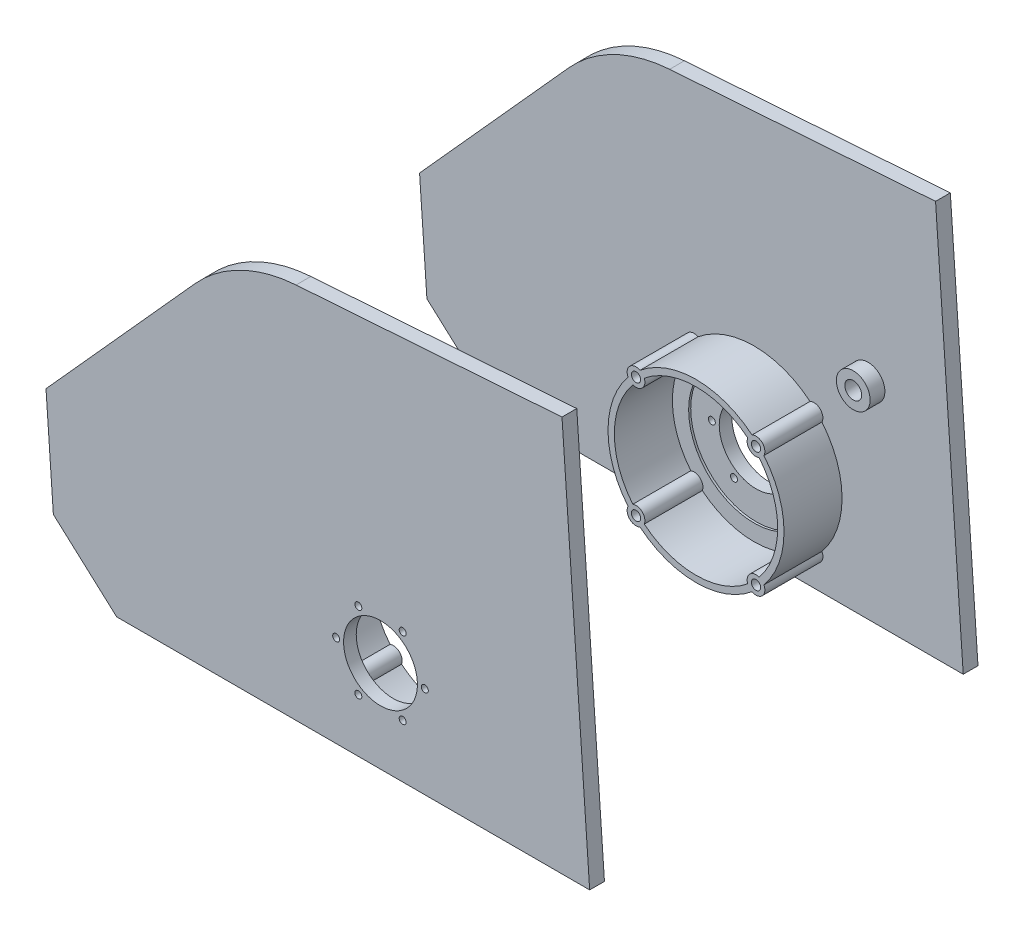
SolidWorks part; units mm, degrees
note: The reader was unsure of these and kept them because the rebuilt part matched: shared geometry of "Sketch4<9>", "Sketch4<11>", "Sketch4<12>", "Sketch2<13>", "Sketch2<14>".
material "ABS"
ref_plane "Front Plane" through (0, 0, 0) normal (0, 0, 1) x (1, 0, 0)
ref_plane "Top Plane" through (0, 0, 0) normal (0, 1, 0) x (1, 0, 0)
ref_plane "Right Plane" through (0, 0, 0) normal (1, 0, 0) x (0, 0, -1)
sketch "Sketch1" plane through (0, 0, 0) normal (0, 0, 1) x (1, 0, 0)
  line L0 (-158.4878, 33.3903) -> (-155, -16.4879)
  line L1 (-155, -16.4879) -> (-125, -43.5)
  line L2 (-125, -43.5) -> (99.1113, -43.5)
  line L3 (-40, 135.1892) -> (86, 144)
  line L5 (-158.4878, 33.3903) -> (-87.8345, 111.8588)
  line L7 (99.1113, -43.5) -> (86, 144)
  line L8 (0, 0) -> (54, 54) construction
  line L11 (-47.6182, 0) -> (49.7288, 0) construction
  line L18 (90.7534, 76.0227) -> (-160.2417, 58.4714) construction
  line L19 (0, -75.7784) -> (0, 71.0771) construction
  circle A0 centre (0, 0) radius 34.5 construction
  circle A1 centre (54, 54) radius 4 construction
  arc A17 (-87.8345, 111.8588) -> (-40, 135.1892) centre (-35.0448, 64.3267) cw
  point P42 (0, 0)
  point P45 (0, 0)
  dimension "D1" = 69
  dimension "D3" = 4
  dimension "D4" = 9
  dimension "D5" = 54
  dimension "D6" = 45
  dimension "D7" = 8
  dimension "D8" = 90
  dimension "D9" = 251.608
  dimension "D10" = 86
  dimension "D11" = 42
  dimension "D12" = 30
  dimension "D13" = 50
  dimension "D14" = 155
  dimension "D15" = 40
  dimension "D23" = 32
extrude "Boss-Extrude1" add sketch "Sketch1" against normal blind 7
sketch "Sketch2" plane through (0, 0, -7) normal (0, 0, -1) x (-1, 0, 0)
  line L0 (-54, 34.6249) -> (-54, 72.2846) construction
  line L1 (-26.529, 54) -> (-79.2855, 54) construction
  line L2 (40, 135.1892) -> (-86, 144) construction
  line L3 (-74, 62) -> (-34, 62) construction
  line L4 (-74, 62) -> (-74, 42) construction
  line L5 (-74, 42) -> (-34, 42) construction
  line L6 (-34, 62) -> (-34, 42) construction
  circle A1 centre (-28.4257, 28.4257) radius 2.2
  circle A2 centre (0, 0) radius 40.2 construction
  arc A4 (-26.529, 32.173) -> (-32.173, 26.529) centre (-28.4257, 28.4257) ccw
  arc A5 (24.5113, 29.9481) -> (29.9481, 24.5113) centre (28.4257, 28.4257) ccw
  circle A6 centre (0, 0) radius 34.5 construction
  circle A7 centre (28.4257, 28.4257) radius 2.2
  arc A8 (29.9481, -24.5113) -> (24.5113, -29.9481) centre (28.4257, -28.4257) ccw
  circle A9 centre (28.4257, -28.4257) radius 2.2
  arc A10 (-32.173, -26.529) -> (-26.529, -32.173) centre (-28.4257, -28.4257) ccw
  circle A11 centre (-28.4257, -28.4257) radius 2.2
  arc A12 (-29.9481, 24.5113) -> (-24.5113, 29.9481) centre (-28.4257, 28.4257) ccw
  arc A13 (-32.173, 26.529) -> (-32.173, -26.529) centre (0, 0) ccw
  arc A14 (-29.9481, 24.5113) -> (-29.9481, -24.5113) centre (0, 0) ccw
  arc A15 (24.5113, 29.9481) -> (-24.5113, 29.9481) centre (0, 0) ccw
  arc A16 (26.529, 32.173) -> (-26.529, 32.173) centre (0, 0) ccw
  circle A17 centre (0, 0) radius 38.7 construction
  arc A18 (32.173, 26.529) -> (26.529, 32.173) centre (28.4257, 28.4257) ccw
  arc A19 (-24.5113, -29.9481) -> (24.5113, -29.9481) centre (0, 0) ccw
  arc A20 (29.9481, -24.5113) -> (29.9481, 24.5113) centre (0, 0) ccw
  arc A21 (-24.5113, -29.9481) -> (-29.9481, -24.5113) centre (-28.4257, -28.4257) ccw
  arc A22 (26.529, -32.173) -> (32.173, -26.529) centre (28.4257, -28.4257) ccw
  arc A23 (-26.529, -32.173) -> (26.529, -32.173) centre (0, 0) ccw
  arc A24 (32.173, -26.529) -> (32.173, 26.529) centre (0, 0) ccw
  circle A25 centre (0, 0) radius 41.7 construction
  circle A26 centre (-70, 54) radius 2.2
  circle A27 centre (-38, 54) radius 2.2
  circle A28 centre (-54, 46) radius 2.2
  circle A29 centre (0, 0) radius 16 construction
  circle A30 centre (0, 0) radius 17.5
  circle A31 centre (0, 0) radius 31
  circle A32 centre (-10.5, 18.1865) radius 1.65
  circle A34 centre (10.5, 18.1865) radius 1.65
  circle A35 centre (21, 0) radius 1.65
  circle A36 centre (10.5, -18.1865) radius 1.65
  circle A37 centre (-10.5, -18.1865) radius 1.65
  circle A38 centre (-21, 0) radius 1.65
  circle A39 centre (-54, 54) radius 4
  circle A40 centre (-54, 54) radius 8
  circle A42 centre (0, 0) radius 21 construction
  point P17 (0, 0)
  point P23 (0, 0)
  point P66 (0, 0)
  dimension "D1" = 1.5
  dimension "D2" = 1.5
  dimension "D3" = 1.5
  dimension "D4" = 4
  dimension "D5" = 2
  dimension "D6" = 4.4
  dimension "D7" = 40
  dimension "D10" = 4.4
  dimension "D13" = 32
  dimension "D14" = 1.5
  dimension "D15" = 42
  dimension "D16" = 62
  dimension "D17" = 3.3
  dimension "D18" = 6
  dimension "D20" = 8
  dimension "D21" = 4
  dimension "D8" = 12
  dimension "D9" = 8
  dimension "D11" = 4
  dimension "D12" = 4
  dimension "D19" = 86.4325
ref_plane "Plane1" through (0, 0, -99) normal (0, 0, 1) x (1, 0, 0)
extrude "Cut-Extrude1" cut sketch "Sketch2" against normal offset from surface (1 mm away) 6 contours A31 up to face at (-54.7827, 46.5142, 0)
extrude "Boss-Extrude2" add sketch "Sketch4<9>" along normal blind 28.5 from surface at -1 contours A23 A22 A24 A18 A16 A4 A13 A10 | A14 A21 A19 A8 A20 A5 A15 A12 starting at face at (-31, 0, -6)
sketch "Sketch4<9>" plane through (0, 0, -7) normal (0, 0, -1) x (-1, 0, 0) same geometry as "Sketch2"
extrude "Cut-Extrude3" cut sketch "Sketch4<11>" against normal blind 6 from surface at 27.5 contours A7 | A11 | A9 | A1 starting at face at (0, 0, -34.5)
sketch "Sketch4<11>" plane through (0, 0, -7) normal (0, 0, -1) x (-1, 0, 0) same geometry as "Sketch2"
extrude "Cut-Extrude4" cut sketch "Sketch4<12>" against normal through all contours A37 | A36 | A35 | A34 | A30 | A32 | A38
sketch "Sketch4<12>" plane through (0, 0, -7) normal (0, 0, -1) x (-1, 0, 0) same geometry as "Sketch2"
extrude "Boss-Extrude3" add sketch "Sketch2<13>" along normal blind 7 contours A40
sketch "Sketch2<13>" plane through (0, 0, -7) normal (0, 0, -1) x (-1, 0, 0) same geometry as "Sketch2"
ref_plane "Plane2" through (0, 0, -92) normal (0, 0, 1) x (1, 0, 0)
extrude "Cut-Extrude5" cut sketch "Sketch2<14>" against normal up to surface (7 mm away) from surface at 7 contours A39 up to face at (46, 54, -7) starting at face at (46, 54, -14)
sketch "Sketch2<14>" plane through (0, 0, -7) normal (0, 0, -1) x (-1, 0, 0) same geometry as "Sketch2"
mirror "Mirror1" about plane through (0, 0, -92) normal (0, 0, 1) of bodies 135 128
split "Split1" trim tools "Plane2" bodies to split 129 135 resulting bodies 130 131
